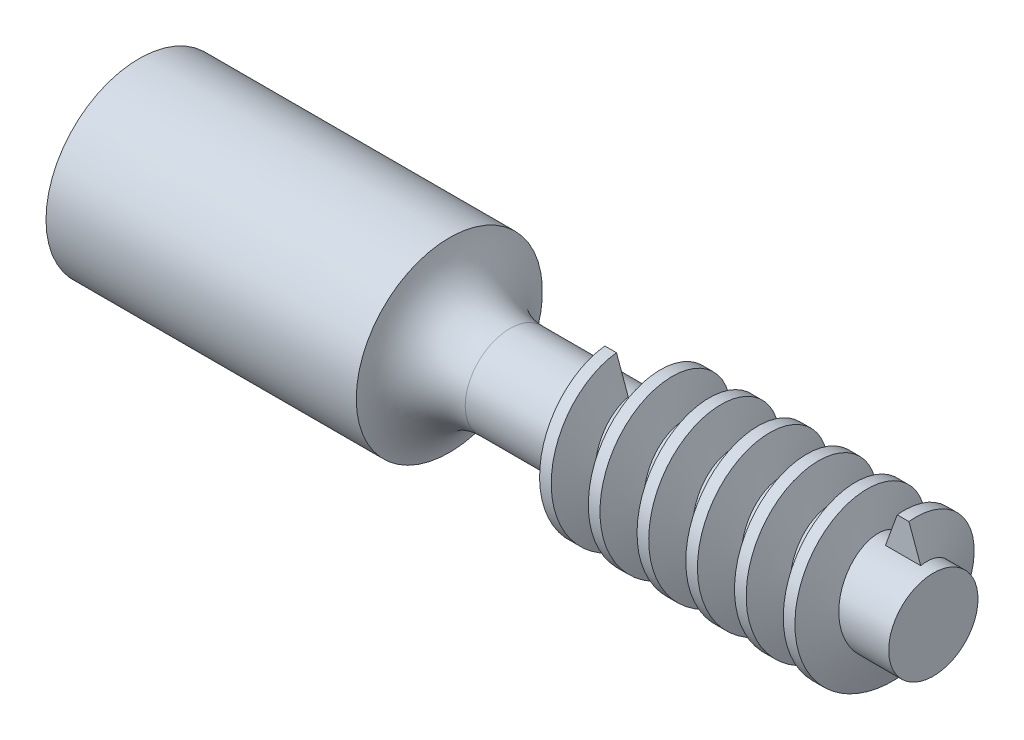
SolidWorks part; units mm, degrees
ref_plane "Front Plane" through (0, 0, 0) normal (0, 0, 1) x (1, 0, 0)
ref_plane "Top Plane" through (0, 0, 0) normal (0, 1, 0) x (1, 0, 0)
ref_plane "Right Plane" through (0, 0, 0) normal (1, 0, 0) x (0, 0, -1)
sketch "Sketch1" plane through (0, 0, 0) normal (0, 0, 1) x (1, 0, 0)
  line L0 (-1.42, 0) -> (1.42, 0) construction
  line L1 (-1.42, 0) -> (-0.47, 2.61)
  line L2 (-0.47, 2.61) -> (0.47, 2.61)
  line L3 (0.47, 2.61) -> (1.42, 0)
  line L4 (-1.42, 0) -> (-2.4, 0) construction
  line L5 (-0.47, 2.61) -> (-3.3499, 2.61) construction
  line L6 (-3.3499, 2.61) -> (-2.4, 0) construction
  line L7 (-1.42, 0) -> (1.42, 0)
  point P8 (0, 0)
  point P10 (0, 2.61)
  dimension "D1" = 70
  dimension "D2" = 70
  dimension "D3" = 0.94
  dimension "D4" = 0.98
  dimension "D5" = 2.61
sketch "Sketch2" plane through (0, 0, 0) normal (1, 0, 0) x (0, 0, -1)
  circle A0 centre (0, -3.599) radius 3.599
  dimension "D1" = 7.198
curve "Helix/Spiral1" pitch 3.927 height 23.5619 radius 3.599 centre (0, -3.599, 0) axis (1, 0, 0) start towards (0, 1, 0)
sweep "Sweep1" add profiles "Sketch1" path "Helix/Spiral1"
extrude "Boss-Extrude1" add sketch "Sketch2<2>" along normal blind 26 and the other way blind 13
sketch "Sketch2<2>" plane through (0, 0, 0) normal (1, 0, 0) x (0, 0, -1) same geometry as "Sketch2"
ref_axis "Axis1" through (26, -3.599, 0) along (-1, 0, 0)
sketch "Sketch3" plane through (-13, 0, 0) normal (-1, 0, 0) x (0, 0, 1)
  circle A2 centre (0, -3.599) radius 7.5
  dimension "D1" = 15
extrude "Boss-Extrude2" add sketch "Sketch3" along normal blind 25
sketch "Sketch4" plane through (-38, 0, 0) normal (-1, 0, 0) x (0, 0, 1)
  line L2 (3.5, -5.5355) -> (3.5, -1.6625)
  line L3 (1.9365, -7.099) -> (-1.9365, -7.099)
  circle A0 centre (0, -3.599) radius 4
  dimension "D1" = 8
  dimension "D2" = 3.5
extrude "Cut-Extrude1" cut sketch "Sketch4" against normal blind 13 contours L2 A0 L3 region at (-38, -3.4974, -0.1016)
fillet "Fillet1" radius 5 1 edges at (-13, -3.599, -3.599)
